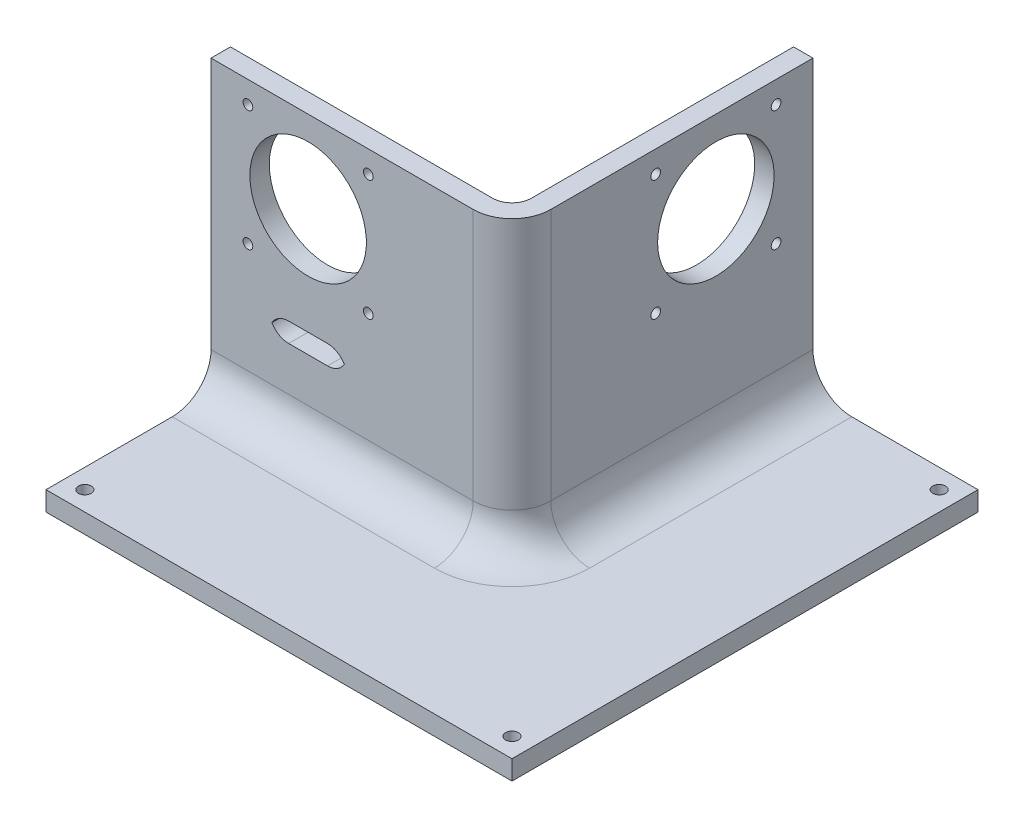
SolidWorks part; units mm, degrees
ref_plane "Front Plane" through (0, 0, 0) normal (0, 0, 1) x (1, 0, 0)
ref_plane "Top Plane" through (0, 0, 0) normal (0, 1, 0) x (1, 0, 0)
ref_plane "Right Plane" through (0, 0, 0) normal (1, 0, 0) x (0, 0, -1)
sketch "Sketch1" plane through (0, 0, 0) normal (0, 1, 0) x (1, 0, 0)
  line L0 (0, 72.5) -> (0, 0)
  line L1 (-72.5, -72.5) -> (72.5, -72.5)
  line L2 (-72.5, -72.5) -> (-72.5, 72.5)
  line L3 (-72.5, 72.5) -> (72.5, 72.5)
  line L4 (72.5, -72.5) -> (72.5, 72.5)
  line L5 (-72.5, -72.5) -> (72.5, 72.5) construction
  line L6 (-72.5, 72.5) -> (72.5, -72.5) construction
  line L7 (0, 0) -> (-72.5, 0)
  line L8 (-72.5, 0) -> (-72.5, -72.5)
  point P0 (0, 0)
  dimension "D1" = 145
  dimension "D2" = 145
extrude "Boss-Extrude1" add sketch "Sketch1" along normal blind 20 contours L0 L7 L2 L1 L4 L3 region at (12.0833, 0, 12.0833)
sketch "Sketch2" plane through (0, 20, 0) normal (0, 1, 0) x (1, 0, 0)
  line L0 (0, 72.5) -> (72.5, 72.5) construction
  line L1 (0, 0) -> (5, 0)
  line L2 (0, 0) -> (0, 72.5)
  line L3 (0, 72.5) -> (5, 72.5)
  line L4 (5, 0) -> (5, 72.5)
  line L5 (0, 0) -> (5, 72.5) construction
  line L6 (0, 72.5) -> (5, 0) construction
  line L7 (0, 0) -> (-72.5, 0) construction
  line L8 (0, 72.5) -> (0, 0) construction
  point P0 (2.5, 36.25)
  dimension "D1" = 0
  dimension "D2" = 0
  dimension "D3" = 0
  dimension "D4" = 5
extrude "Boss-Extrude2" add sketch "Sketch2" along normal blind 60
sketch "Sketch3" plane through (0, 0, 0) normal (-1, 0, 0) x (0, 0, 1)
  line L0 (-72.5, 80) -> (0, 80) construction
  line L1 (-72.5, 80) -> (-72.5, 0) construction
  circle A0 centre (-47.5, 58.85) radius 15
  dimension "D3" = 30
  dimension "D1" = 21.15
  dimension "D2" = 25
extrude "Cut-Extrude1" cut sketch "Sketch3" against normal blind 100
sketch "Sketch4" plane through (0, 0, 0) normal (-1, 0, 0) x (0, 0, 1)
  line L0 (-72.5, 80) -> (0, 80) construction
  line L1 (-72.5, 80) -> (-72.5, 0) construction
  circle A0 centre (-32, 74.35) radius 1.25
  circle A1 centre (-63, 74.35) radius 1.25
  circle A2 centre (-63, 43.35) radius 1.25
  circle A3 centre (-32, 43.35) radius 1.25
  point P12 (-32, 43.35)
  dimension "D3" = 2.5
  dimension "D6" = 2.5
  dimension "D9" = 2.5
  dimension "D12" = 2.5
  dimension "D2" = 5.65
  dimension "D4" = 31
  dimension "D5" = 9.5
  dimension "D7" = 31
  dimension "D8" = 0
  dimension "D10" = 0
  dimension "D11" = 0
  dimension "D13" = 31
extrude "Cut-Extrude2" cut sketch "Sketch4" against normal blind 100
sketch "Sketch7" plane through (0, 20, 0) normal (0, 1, 0) x (1, 0, 0)
  line L1 (-72.5, 0) -> (5, 0)
  line L2 (-72.5, 0) -> (-72.5, -5)
  line L3 (-72.5, -5) -> (5, -5)
  line L4 (5, 0) -> (5, -5)
  dimension "D1" = 5
  dimension "D2" = 0
extrude "Boss-Extrude6" add sketch "Sketch7" along normal blind 60
ref_plane "Plane2" through (0, 0, 0) normal (-0.7071, 0, 0.7071) x (0.7071, 0, 0.7071)
mirror "Mirror5" about plane through (0, 0, 0) normal (-0.7071, 0, 0.7071) of "Cut-Extrude2", "Cut-Extrude1"
fillet "Fillet3" radius 5 1 edges at (0, 40, 0)
sketch "Sketch8" plane through (0, 20, 0) normal (0, 1, 0) x (1, 0, 0)
  line L0 (-72.5, -72.5) -> (72.5, -72.5) construction
  line L1 (47.5, -72.5) -> (72.5, -72.5)
  line L2 (47.5, -72.5) -> (47.5, 72.5)
  line L3 (47.5, 72.5) -> (72.5, 72.5)
  line L4 (72.5, -72.5) -> (72.5, 72.5)
  line L5 (47.5, -72.5) -> (72.5, 72.5) construction
  line L6 (47.5, 72.5) -> (72.5, -72.5) construction
  line L7 (72.5, -47.5) -> (-72.5, -47.5)
  line L8 (72.5, -47.5) -> (72.5, -72.5)
  line L9 (72.5, -72.5) -> (-72.5, -72.5)
  line L10 (-72.5, -47.5) -> (-72.5, -72.5)
  line L11 (72.5, -47.5) -> (-72.5, -72.5) construction
  line L12 (72.5, -72.5) -> (-72.5, -47.5) construction
  point P0 (60, 0)
  point P6 (0, -60)
  line M7 (-72.5, -5) -> (-72.5, -72.5)
  line M8 (-72.5, -72.5) -> (72.5, -72.5)
  line M9 (72.5, -72.5) -> (72.5, 72.5)
  line M10 (72.5, 72.5) -> (5, 72.5)
  dimension "D1" = 0
  dimension "D2" = 0
  dimension "D3" = 25
  dimension "D4" = 25
extrude "Cut-Extrude3" cut sketch "Sketch8" against normal blind 100 contours L7 L4 L2 M10 | L7 L2 M9 M8 | L2 L7 M7 M8 region at (60, 20, 60) region at (-12.5, 20, 60) region at (60, 20, -12.5)
sketch "Sketch9" plane through (0, 20, 0) normal (0, 1, 0) x (1, 0, 0)
  line L0 (47.5, -47.5) -> (47.5, 72.5) construction
  line L1 (5, 72.5) -> (47.5, 72.5) construction
  line L2 (47.5, -47.5) -> (-72.5, -47.5) construction
  line L4 (-72.5, -47.5) -> (-72.5, -5) construction
  circle A0 centre (42.5, 67.5) radius 1.65
  circle A1 centre (42.5, -42.5) radius 1.65
  circle A2 centre (-67.5, -42.5) radius 1.65
  dimension "D3" = 3.3
  dimension "D6" = 3.3
  dimension "D8" = 3.3
  dimension "D1" = 5
  dimension "D2" = 5
  dimension "D4" = 0
  dimension "D5" = 5
  dimension "D7" = 0
  dimension "D9" = 5
extrude "Cut-Extrude4" cut sketch "Sketch9" against normal blind 100
sketch "Sketch10" plane through (0, 20, 0) normal (0, 1, 0) x (1, 0, 0)
  line L0 (-72.5, -5) -> (5, -5) construction
  line L1 (47.5, -47.5) -> (5, -47.5)
  line L2 (47.5, -47.5) -> (47.5, 72.5)
  line L3 (47.5, 72.5) -> (5, 72.5)
  line L4 (5, -47.5) -> (5, 72.5)
  line L5 (47.5, -47.5) -> (5, 72.5) construction
  line L6 (47.5, 72.5) -> (5, -47.5) construction
  line L7 (47.5, -5) -> (-72.5, -5)
  line L8 (47.5, -5) -> (47.5, -47.5)
  line L9 (47.5, -47.5) -> (-72.5, -47.5)
  line L10 (-72.5, -5) -> (-72.5, -47.5)
  line L11 (47.5, -5) -> (-72.5, -47.5) construction
  line L12 (47.5, -47.5) -> (-72.5, -5) construction
  line L13 (47.5, -47.5) -> (47.5, 72.5) construction
  point P0 (26.25, 12.5)
  point P6 (-12.5, -26.25)
  dimension "D1" = 0
  dimension "D2" = 0
  dimension "D3" = 0
  dimension "D4" = 0
extrude "Cut-Extrude5" cut sketch "Sketch10" against normal blind 15 contours L2 L1 L4 L3 | L8 L7 L10 L9
fillet "Fillet4" radius 10 3 edges at (5, 42.5, 5) (-33.75, 5, 5) (5, 5, -33.75)
sketch "Sketch11" plane through (0, 0, 5) normal (0, 0, 1) x (1, 0, 0)
  line L1 (-57.5, 26.35) -> (-37.5, 26.35)
  line L2 (-57.5, 26.35) -> (-57.5, 31.35)
  line L3 (-57.5, 31.35) -> (-37.5, 31.35)
  line L4 (-37.5, 26.35) -> (-37.5, 31.35)
  line L5 (-57.5, 26.35) -> (-37.5, 31.35) construction
  line L6 (-57.5, 31.35) -> (-37.5, 26.35) construction
  circle A0 centre (-47.5, 58.85) radius 15 construction
  point P0 (-47.5, 28.85)
  dimension "D1" = 0
  dimension "D2" = 30
  dimension "D3" = 5
  dimension "D4" = 20
extrude "Cut-Extrude6" cut sketch "Sketch11" against normal blind 6
fillet "Fillet5" radius 5 4 edges at (-57.5, 26.35, 2.5) (-57.5, 31.35, 2.5) (-37.5, 31.35, 2.5) (-37.5, 26.35, 2.5)
